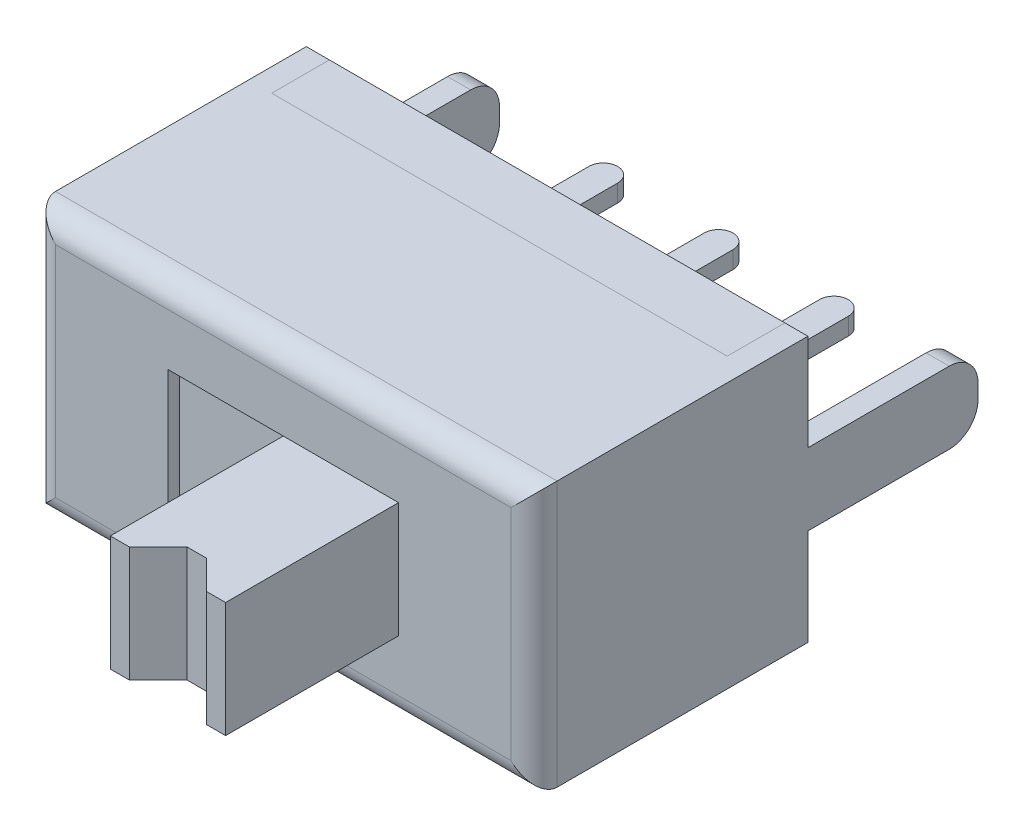
SolidWorks part; units mm, degrees
ref_plane "Front Plane" through (0, 0, 0) normal (0, 0, 1) x (1, 0, 0)
ref_plane "Top Plane" through (0, 0, 0) normal (0, 1, 0) x (1, 0, 0)
ref_plane "Right Plane" through (0, 0, 0) normal (1, 0, 0) x (0, 0, -1)
sketch "Sketch1" plane through (0, 0, 0) normal (0, 0, 1) x (1, 0, 0)
  line L1 (-4.35, 2.3) -> (4.35, 2.3)
  line L2 (-4.35, 2.3) -> (-4.35, -2.3)
  line L3 (-4.35, -2.3) -> (4.35, -2.3)
  line L4 (4.35, 2.3) -> (4.35, -2.3)
  line L5 (-4.35, 2.3) -> (4.35, -2.3) construction
  line L6 (-4.35, -2.3) -> (4.35, 2.3) construction
  point P0 (0, 0)
  dimension "D1" = 8.7
  dimension "D2" = 4.6
extrude "Boss-Extrude1" add sketch "Sketch1" along normal blind 4.75
fillet "Fillet2" radius 0.4 4 edges at (-4.35, 0, 4.75) (0, 2.3, 4.75) (4.35, 0, 4.75) (0, -2.3, 4.75)
sketch "Sketch2" plane through (0, 0, 4.75) normal (0, 0, 1) x (1, 0, 0)
  line L1 (-2, 1) -> (2, 1)
  line L2 (-2, 1) -> (-2, -1)
  line L3 (-2, -1) -> (2, -1)
  line L4 (2, 1) -> (2, -1)
  line L5 (-2, 1) -> (2, -1) construction
  line L6 (-2, -1) -> (2, 1) construction
  point P0 (0, 0)
  dimension "D1" = 2
  dimension "D2" = 4
extrude "Cut-Extrude1" cut sketch "Sketch2" against normal blind 0.2
sketch "Sketch4" plane through (0, -1, 0) normal (0, 1, 0) x (1, 0, 0)
  line L0 (2, -4.55) -> (2, -7.75)
  line L1 (2, -7.75) -> (1.6667, -7.75)
  line L2 (1.6667, -7.75) -> (1.1667, -7.25)
  line L3 (1.1667, -7.25) -> (0.8333, -7.25)
  line L4 (0.8333, -7.25) -> (0.3333, -7.75)
  line L5 (0.3333, -7.75) -> (0, -7.75)
  line L6 (0, -7.75) -> (0, -4.55)
  line L7 (2, -4.55) -> (-2, -4.55) construction
  line L8 (0, -4.55) -> (2, -4.55)
  line L9 (3.95, -4.75) -> (-3.95, -4.75) construction
  dimension "D1" = 2
  dimension "D2" = 3
  dimension "D3" = 45
  dimension "D4" = 0.5
extrude "Boss-Extrude2" add sketch "Sketch4" along normal up to surface (2 mm away) up to face at (0, 1, 4.65)
sketch "Sketch8" plane through (0, 0, 0) normal (0, 0, -1) x (-1, 0, 0)
  line L0 (-4.35, 2.3) -> (4.35, 2.3) construction
  line L1 (3.95, -2.3) -> (-3.95, -2.3)
  line L2 (3.95, -2.3) -> (3.95, 2.3)
  line L3 (3.95, 2.3) -> (-3.95, 2.3)
  line L4 (-3.95, -2.3) -> (-3.95, 2.3)
  line L5 (3.95, -2.3) -> (-3.95, 2.3) construction
  line L6 (3.95, 2.3) -> (-3.95, -2.3) construction
  line L7 (-4.35, -2.3) -> (-4.35, 2.3) construction
  point P0 (0, 0)
  dimension "D1" = 0.4
extrude "Cut-Extrude2" cut sketch "Sketch8" against normal blind 1
sketch "Sketch5" plane through (0, 0, 0) normal (0, 0, -1) x (-1, 0, 0)
  line L0 (-4.35, -2.3) -> (-4.35, 2.3) construction
  line L1 (-4.35, 0.625) -> (-3.95, 0.625)
  line L2 (-4.35, 0.625) -> (-4.35, -0.625)
  line L3 (-4.35, -0.625) -> (-3.95, -0.625)
  line L4 (-3.95, 0.625) -> (-3.95, -0.625)
  line L5 (0, 0) -> (-3.95, 0) construction
  dimension "D1" = 1.25
  dimension "D2" = 0.4
extrude "Boss-Extrude3" add sketch "Sketch5" along normal offset from surface (2.95 mm away) 7.7 up to face at (0, 0, 4.75)
fillet "Fillet3" radius 0.5 2 edges at (4.15, -0.625, -2.95) (4.15, 0.625, -2.95)
mirror "Mirror1" about plane through (0, 0, 0) normal (1, 0, 0) of "Fillet3", "Boss-Extrude3"
sketch "Sketch10" plane through (0, 0, 1) normal (0, 0, -1) x (-1, 0, 0)
  line L1 (-0.25, 0.15) -> (0.25, 0.15)
  line L2 (-0.25, 0.15) -> (-0.25, -0.15)
  line L3 (-0.25, -0.15) -> (0.25, -0.15)
  line L4 (0.25, 0.15) -> (0.25, -0.15)
  line L5 (-0.25, 0.15) -> (0.25, -0.15) construction
  line L6 (-0.25, -0.15) -> (0.25, 0.15) construction
  point P0 (0, 0)
  dimension "D1" = 0.5
  dimension "D2" = 0.3
extrude "Boss-Extrude6" add sketch "Sketch10" along normal offset from surface (4.05 mm away) 7.8 up to face at (0, 0, 4.75)
fillet "Fillet5" 2 edges at (0.25, 0, -3.05) (-0.25, 0, -3.05) type full round first side face at (0.25, 0, -1.025) second side face at (-0.25, 0, -1.025) middle face at (0, 0, -3.05)
pattern_linear "LPattern3" count 2 spacing 2 along (1, 0, 0) count 2 spacing 2 along (-1, 0, 0) of "Boss-Extrude6", "Fillet5" pattern seed only yes
sketch "Sketch9" plane through (0, 0, 1) normal (0, 0, -1) x (-1, 0, 0)
  line L1 (-3.95, 2.3) -> (3.95, 2.3)
  line L2 (-3.95, 2.3) -> (-3.95, -2.3)
  line L3 (-3.95, -2.3) -> (3.95, -2.3)
  line L4 (3.95, 2.3) -> (3.95, -2.3)
extrude "Boss-Extrude7" add sketch "Sketch9" along normal blind 1 separate body
